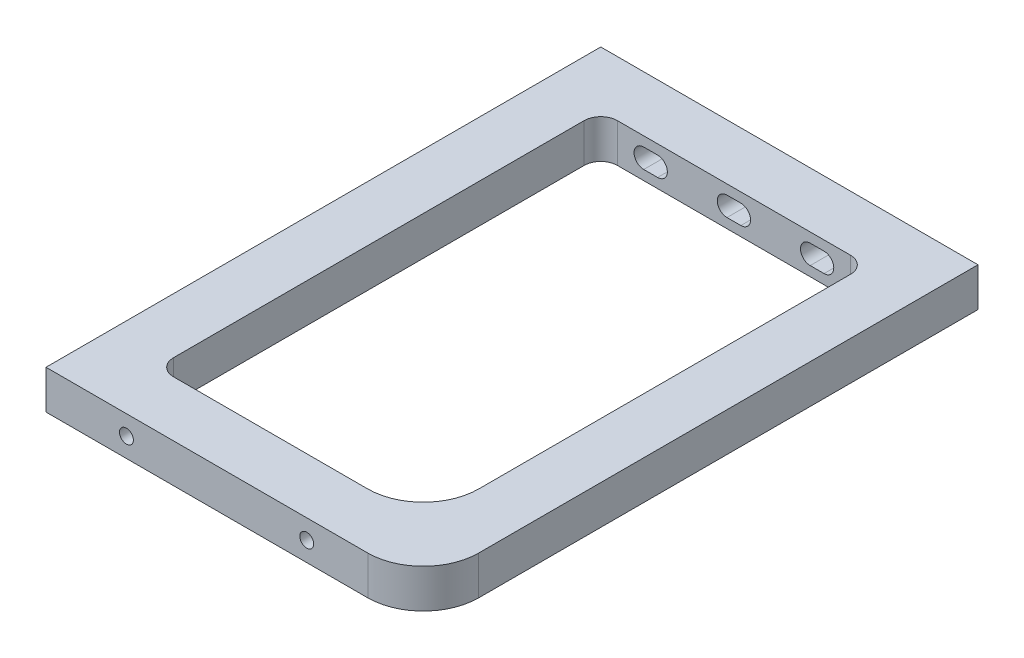
SolidWorks part; units mm, degrees
other "Markup1"
sketch "Sketch11" plane through (-148, 207, 138) normal (-0.4174, 0.5856, 0.6948) x (0.7295, -0.24, 0.6405)
ref_plane "Front Plane" through (0, 0, 0) normal (0, 0, 1) x (1, 0, 0)
ref_plane "Top Plane" through (0, 0, 0) normal (0, 1, 0) x (1, 0, 0)
ref_plane "Right Plane" through (0, 0, 0) normal (1, 0, 0) x (0, 0, -1)
sketch "Sketch1" plane through (0, 0, 0) normal (0, 0, 1) x (1, 0, 0)
  line L1 (-148, 235) -> (-148, 170) construction
  line L4 (-148, 207) -> (-21, 207)
  line L8 (-148, 197.5) -> (-148, 193)
  line L10 (-148, 197.5) -> (-148, 207)
  line L11 (-148, 193) -> (-24, 193)
  line L13 (-148, 207) -> (-21, 207)
  line L16 (-21, 207) -> (-12, 207)
  line L17 (-12, 207) -> (-12, 193)
  line L18 (-12, 193) -> (-24, 193)
extrude "Boss-Extrude1" add sketch "Sketch1" along normal up to surface (200 mm away) region at (-80, 200, 0)
sketch "Sketch3" plane through (0, 207, 0) normal (0, 1, 0) x (1, 0, 0)
  line L0 (-128, -30) -> (-128, -20)
  line L1 (-128, -108) -> (-128, -180)
  line L2 (-128, -180) -> (-118, -180)
  line L3 (-54, -180) -> (-32, -180)
  line L4 (-32, -180) -> (-32, -20)
  line L5 (-32, -180) -> (-32, -20)
  line L6 (-32, -20) -> (-128, -20)
  line L7 (-32, -20) -> (-128, -20)
  line L12 (-128, -20) -> (-128, -180)
  line L13 (-128, -20) -> (-128, -180)
  line L23 (-128, -180) -> (-32, -180)
  line L27 (-118, -180) -> (-54, -180)
  dimension "D1" = 20
extrude "Cut-Extrude1" cut sketch "Sketch3" against normal through all contours L7 L13 L27 region at (-80, 207, 100)
sketch "Sketch5" plane through (0, 0, 20) normal (0, 0, 1) x (1, 0, 0)
  circle A3 centre (-110, 200) radius 3
  circle A4 centre (-80, 200) radius 3
  circle A5 centre (-50, 200) radius 3
hole_wizard "Ø6.0mm Dowel Slot1" positions "Sketch6" profile "Sketch7" size "Ø6.0" standard "ANSI Metric" slot yes end condition through all
sketch "Sketch6" plane through (0, 0, 20) normal (0, 0, 1) x (1, 0, 0)
  line L0 (-116, 200) -> (-104, 200) construction
  point P12 (-110, 200)
  point P15 (-80, 200)
  point P18 (-50, 200)
  dimension "D1" = 12
sketch "Sketch7" plane through (-110, 200, 20) normal (1, 0, 0) x (0, -1, 0)
  line L0 (0, 0) -> (0, 20)
  line L1 (0, 20) -> (3.5, 20)
  line L2 (3.5, 20) -> (3.5, 0)
  line L5 (3.5, 0) -> (0, 0)
  line L11 (0, -6.35) -> (0, 107.95) construction
  dimension "Thru Hole Dia." = 7
  dimension "Thru Hole Depth" = 20
sketch "Sketch8" plane through (0, 0, 200) normal (0, 0, 1) x (1, 0, 0)
  line L0 (-48, 200) -> (-54, 200)
  line L2 (-148, 200) -> (-119, 200)
hole_wizard "M6x1.0 Tapped Hole1" positions "Sketch9" profile "Sketch10" tap size "M6x1.0" standard "ANSI Metric"
sketch "Sketch9" plane through (0, 0, 200) normal (0, 0, 1) x (1, 0, 0)
  point P0 (-119, 200)
  point P3 (-54, 200)
sketch "Sketch10" plane through (-119, 200, 200) normal (1, 0, 0) x (0, -1, 0)
  line L0 (0, 0) -> (0, 23)
  line L1 (0, 23) -> (2.5, 21.4978)
  line L2 (2.5, 21.4978) -> (2.5, 0)
  line L5 (2.5, 0) -> (0, 0)
  line L10 (0, 23) -> (-2.5, 21.4978) construction
  line L11 (0, -6.35) -> (0, 107.95) construction
  dimension "Tap Drill Dia." = 5
  dimension "Tap Drill Depth" = 23
  dimension "Drill Angle" = 118
cosmetic thread "Hole Thread1" parameters "D1"=20, "D2"=6
cosmetic thread "Hole Thread2" parameters "D1"=20, "D2"=6
fillet "Fillet1" radius 6 3 edges at (-128, 200, 180) (-128, 200, 20) (-32, 200, 20)
fillet "Fillet2" radius 20 2 edges at (-12, 200, 200) (-32, 200, 180)
